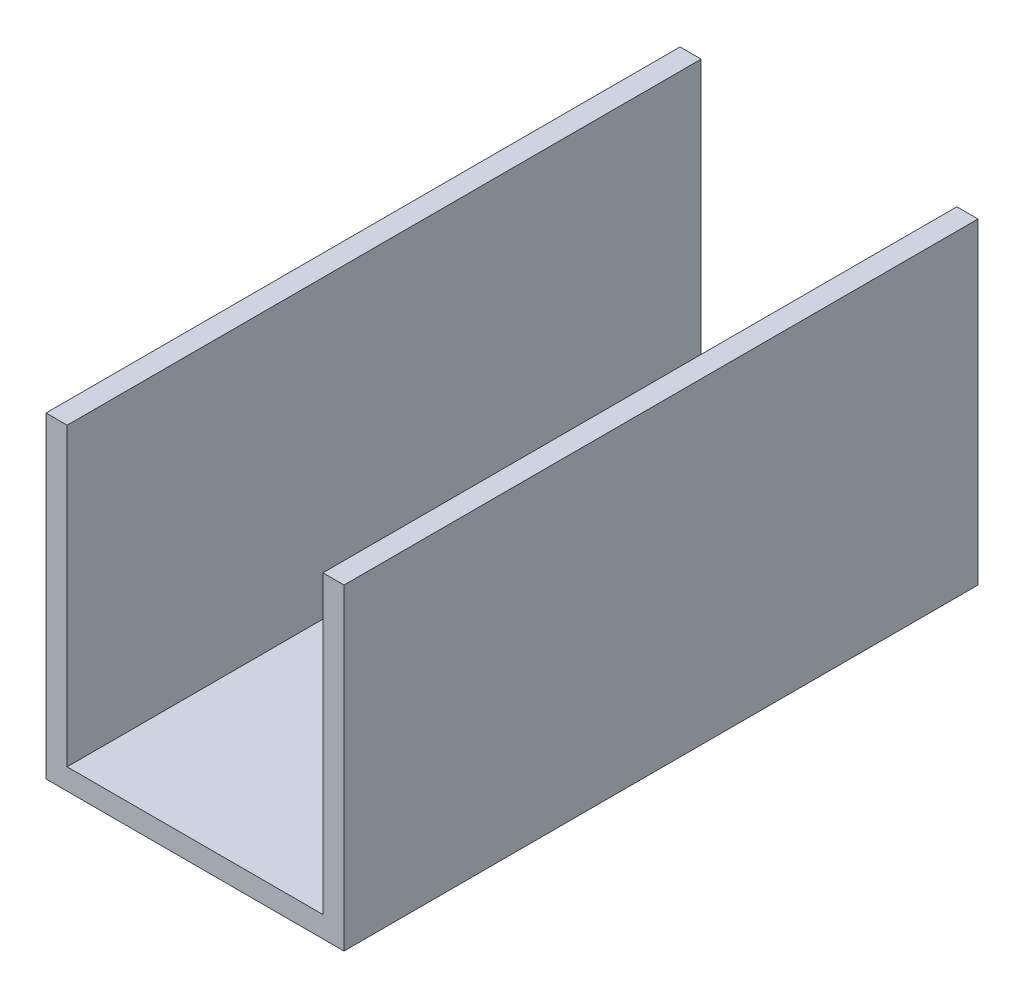
SolidWorks part; units mm, degrees
material "PLA"
ref_plane "Front Plane" through (0, 0, 0) normal (0, 0, 1) x (1, 0, 0)
ref_plane "Top Plane" through (0, 0, 0) normal (0, 1, 0) x (1, 0, 0)
ref_plane "Right Plane" through (0, 0, 0) normal (1, 0, 0) x (0, 0, -1)
sketch "Sketch2" plane through (0, 0, 0) normal (0, 0, 1) x (1, 0, 0)
  line L0 (-24.2, 0) -> (24.2, 0)
  line L1 (-24.2, 0) -> (-24.2, 56)
  line L2 (-24.2, 56) -> (-28.2, 56)
  line L3 (-28.2, 56) -> (-28.2, -4)
  line L4 (-28.2, -4) -> (28.2, -4)
  line L5 (28.2, -4) -> (28.2, 56)
  line L6 (28.2, 56) -> (24.2, 56)
  line L7 (24.2, 56) -> (24.2, 0)
  point P4 (0, 0)
  dimension "D1" = 48.4
  dimension "D2" = 4
  dimension "D3" = 4
  dimension "D4" = 60
  dimension "D5" = 56.4
  dimension "D6" = 60
extrude "Boss-Extrude1" add sketch "Sketch2" along normal mid plane 120
